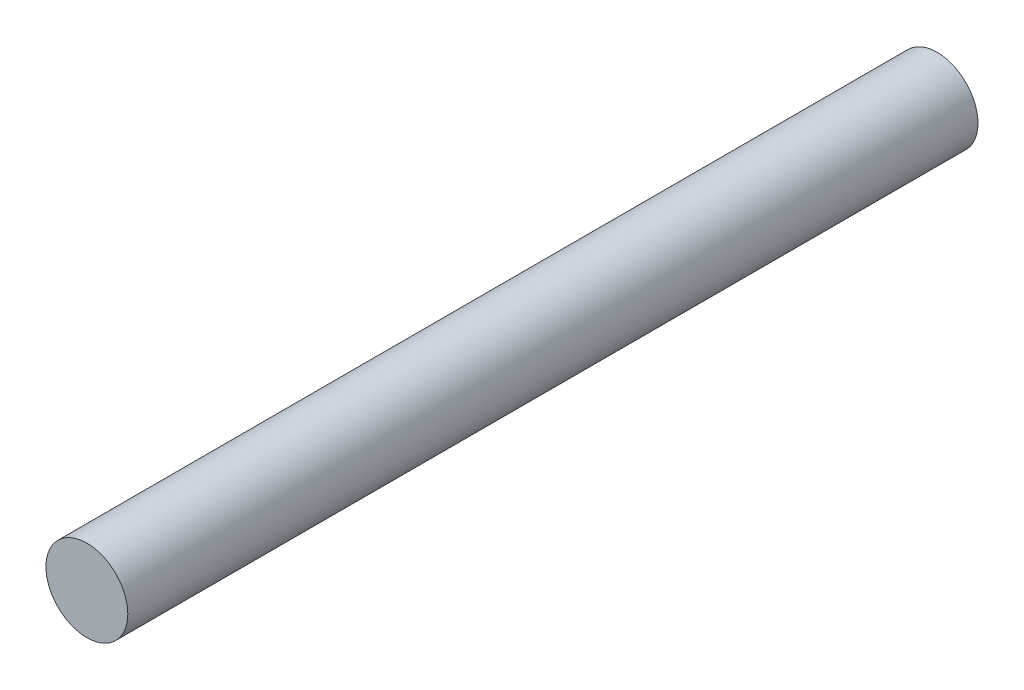
SolidWorks part; units mm, degrees
ref_plane "前视基准面" through (0, 0, 0) normal (0, 0, 1) x (1, 0, 0)
ref_plane "上视基准面" through (0, 0, 0) normal (0, 1, 0) x (1, 0, 0)
ref_plane "右视基准面" through (0, 0, 0) normal (1, 0, 0) x (0, 0, -1)
other "Configuration Table"
sketch "草图1" plane through (0, 0, 0) normal (0, 0, 1) x (1, 0, 0)
  line L0 (0, 0) -> (-6.2607, 0) construction
  line L1 (0, 0) -> (6.2607, 0) construction
  circle A0 centre (0, 0) radius 6.2607
  dimension "D1" = 12.5213
extrude "凸台-拉伸1" add sketch "草图1" along normal blind 130
